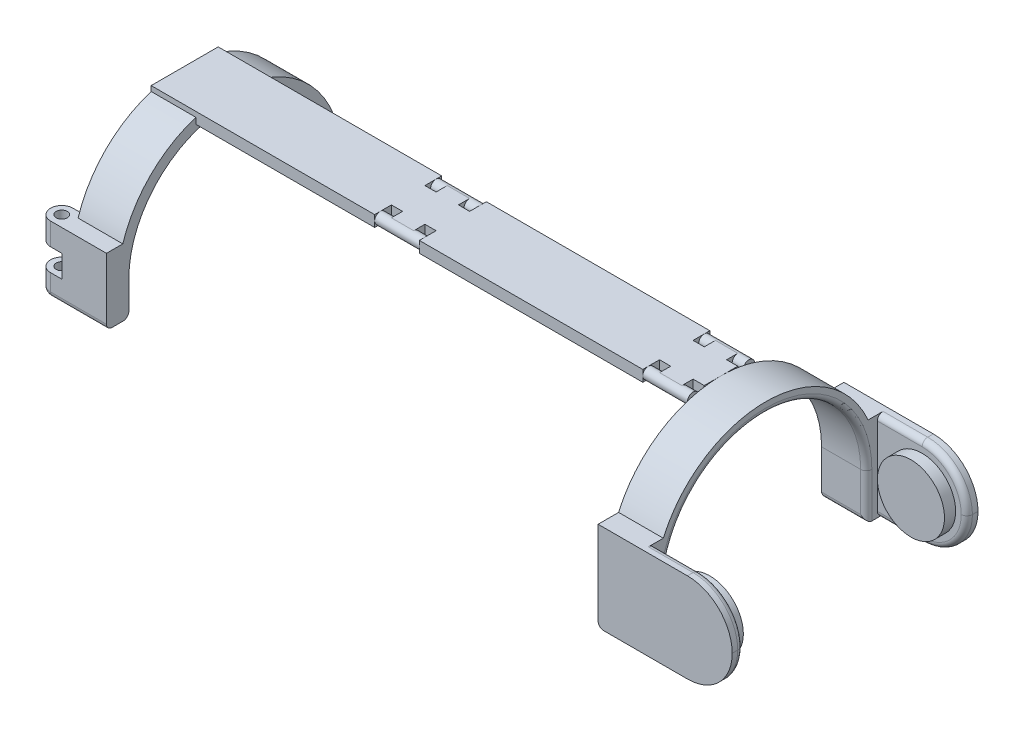
SolidWorks part; units mm, degrees
ref_plane "Front Plane" through (0, 0, 0) normal (0, 0, 1) x (1, 0, 0)
ref_plane "Top Plane" through (0, 0, 0) normal (0, 1, 0) x (1, 0, 0)
ref_plane "Right Plane" through (0, 0, 0) normal (1, 0, 0) x (0, 0, -1)
sketch "Sketch1" plane through (0, 0, 0) normal (1, 0, 0) x (0, 0, -1)
  line L0 (-45, 0) -> (-50, 0)
  line L1 (45, 0) -> (50, 0)
  arc A0 (-50, 0) -> (50, 0) centre (0, 0) cw
  arc A1 (-45, 0) -> (45, 0) centre (0, 0) cw
  dimension "D1" = 50
  dimension "D2" = 45
extrude "Boss-Extrude1" add sketch "Sketch1" along normal blind 20
sketch "Sketch3" plane through (0, 0, 0) normal (1, 0, 0) x (0, 0, -1)
  line L0 (45, 0) -> (50, 0) construction
  line L1 (45, -20) -> (55, -20)
  line L2 (45, -20) -> (45, 20)
  line L3 (45, 20) -> (55, 20)
  line L4 (55, -20) -> (55, 20)
  dimension "D1" = 40
  dimension "D2" = 10
  dimension "D3" = 20
extrude "Boss-Extrude2" add sketch "Sketch3" along normal blind 60
sketch "Sketch4" plane through (0, 0, -45) normal (0, 0, 1) x (1, 0, 0)
  line L0 (60, -20) -> (0, -20) construction
  line L1 (60, 20) -> (20, 20)
  line L2 (60, 20) -> (60, -20)
  line L3 (60, -20) -> (20, -20)
  line L4 (20, 20) -> (20, -20)
extrude "Cut-Extrude1" cut sketch "Sketch4" against normal blind 5
sketch "Sketch5" plane through (0, 0, -50) normal (0, 0, 1) x (1, 0, 0)
  line L0 (60, -20) -> (60, 20) construction
  line L1 (60, 20) -> (20, 20) construction
  circle A0 centre (40, 0) radius 15
  dimension "D1" = 30
  dimension "D2" = 20
  dimension "D3" = 20
extrude "Boss-Extrude3" add sketch "Sketch5" along normal blind 5
sketch "Sketch6" plane through (0, 0, 0) normal (-1, 0, 0) x (0, 0, 1)
  line L1 (0, 45) -> (-7.5, 45)
  line L2 (0, 45) -> (0, 50)
  line L3 (0, 50) -> (-7.5, 50)
  line L4 (-7.5, 45) -> (-7.5, 50)
  arc A0 (45, 0) -> (-45, 0) centre (0, 0) ccw construction
  dimension "D1" = 7.5
extrude "Boss-Extrude4" add sketch "Sketch6" along normal blind 20
sketch "Sketch7" plane through (0, 0, -7.5) normal (0, 0, -1) x (-1, 0, 0)
  line L0 (20, 50) -> (0, 50) construction
  line L1 (5, 50) -> (15, 50)
  line L2 (5, 50) -> (5, 45)
  line L3 (5, 45) -> (15, 45)
  line L4 (15, 50) -> (15, 45)
  line L5 (20, 45) -> (0, 45) construction
  line L6 (0, 49.4343) -> (0, 45) construction
  dimension "D1" = 10
  dimension "D2" = 5
extrude "Boss-Extrude5" add sketch "Sketch7" along normal blind 5
sketch "Sketch9" plane through (0, 0, 0) normal (1, 0, 0) x (0, 0, -1)
  line L0 (12.5, 45) -> (12.5, 50) construction
  circle A0 centre (12.5, 47.5) radius 2.5
  dimension "D1" = 5
extrude "Boss-Extrude6" add sketch "Sketch9" against normal blind 20
mirror "Mirror1" about plane through (0, 0, 0) normal (0, 0, 1) of "Boss-Extrude6", "Boss-Extrude5", "Boss-Extrude4", "Boss-Extrude3", "Cut-Extrude1", "Boss-Extrude2"
fillet "Fillet2" radius 2.5 7 edges at (20, 45, 0) (10, -20, 45) (20, -10, 45) (0, -20, -50) (10, -20, -45) (20, -10, -45) (0, -20, 50)
fillet "Fillet3" radius 20 4 edges at (60, -20, -52.5) (60, 20, -52.5) (60, -20, 52.5) (60, 20, 52.5)
fillet "Fillet4" radius 2.5 8 edges at (30, -20, -50) (54.1421, -14.1421, -50) (54.1421, 14.1421, -50) (30, -20, 50) (54.1421, -14.1421, 50) (54.1421, 14.1421, 50) (30, 20, -50) (30, 20, 50)
sketch "Sketch10" plane through (-20, 0, 0) normal (-1, 0, 0) x (0, 0, 1)
  line L0 (7.5, 50) -> (7.5, 45) construction
  line L1 (15, 45) -> (-15, 45)
  line L2 (15, 45) -> (15, 50)
  line L3 (15, 50) -> (-15, 50)
  line L4 (-15, 45) -> (-15, 50)
  line L6 (-7.5, 50) -> (-7.5, 45) construction
  point P6 (-7.5, 47.5)
  dimension "D1" = 30
  dimension "D2" = 7.5
  dimension "D3" = 5
  dimension "D4" = 2.5
extrude "Boss-Extrude9" add sketch "Sketch10" along normal blind 100
sketch "Sketch12" plane through (-120, 0, 0) normal (-1, 0, 0) x (0, 0, 1)
  line L0 (15, 50) -> (-15, 50) construction
  line L1 (-7.5, 50) -> (0, 50)
  line L2 (-7.5, 50) -> (-7.5, 45)
  line L3 (-7.5, 45) -> (0, 45)
  line L4 (0, 50) -> (0, 45)
  line L5 (-15, 45) -> (15, 45) construction
  line L6 (-15, 50) -> (-15, 45) construction
  dimension "D1" = 7.5
  dimension "D2" = 7.5
extrude "Boss-Extrude10" add sketch "Sketch12" along normal blind 20
sketch "Sketch13" plane through (0, 0, -7.5) normal (0, 0, -1) x (-1, 0, 0)
  line L0 (140, 50) -> (120, 50) construction
  line L1 (125, 50) -> (135, 50)
  line L2 (125, 50) -> (125, 45)
  line L3 (125, 45) -> (135, 45)
  line L4 (135, 50) -> (135, 45)
  line L5 (140, 45) -> (120, 45) construction
  line L6 (120, 50) -> (120, 45) construction
  dimension "D1" = 10
  dimension "D2" = 5
extrude "Boss-Extrude11" add sketch "Sketch13" along normal blind 5
sketch "Sketch14" plane through (-135, 0, 0) normal (-1, 0, 0) x (0, 0, 1)
  line L0 (-12.5, 45) -> (-12.5, 50) construction
  circle A0 centre (-12.5, 47.5) radius 2.5
  dimension "D1" = 5
extrude "Boss-Extrude12" add sketch "Sketch14" along normal blind 5 and the other way blind 15
mirror "Mirror2" about plane through (-140, 50, 0) normal (0, 0, -1) of "Boss-Extrude12", "Boss-Extrude11", "Boss-Extrude10"
sketch "Sketch15" plane through (-140, 0, 0) normal (-1, 0, 0) x (0, 0, 1)
  line L1 (15, 45) -> (-15, 45)
  line L2 (15, 45) -> (15, 50)
  line L3 (15, 50) -> (-15, 50)
  line L4 (-15, 45) -> (-15, 50)
extrude "Boss-Extrude13" add sketch "Sketch15" along normal blind 100
sketch "Sketch16" plane through (-240, 0, 0) normal (-1, 0, 0) x (0, 0, 1)
  line L0 (50, 0) -> (45, 0)
  line L1 (-45, 0) -> (-50, 0)
  arc A0 (45, 0) -> (-45, 0) centre (0, 0) ccw
  arc A1 (0, 45) -> (-45, 0) centre (0, 0) ccw construction
  arc A2 (50, 0) -> (-50, 0) centre (0, 0) ccw
  dimension "D1" = 50
extrude "Boss-Extrude14" add sketch "Sketch16" against normal blind 20
sketch "Sketch17" plane through (-240, 0, 0) normal (-1, 0, 0) x (0, 0, 1)
  line L1 (45, 0) -> (55, 0)
  line L2 (45, 0) -> (45, 15)
  line L3 (45, 15) -> (55, 15)
  line L4 (55, 0) -> (55, 15)
  dimension "D1" = 15
  dimension "D2" = 10
extrude "Boss-Extrude15" add sketch "Sketch17" against normal blind 20 and the other way blind 10
sketch "Sketch18" plane through (0, 0, 55) normal (0, 0, 1) x (1, 0, 0)
  line L1 (-250, 0) -> (-240, 0)
  line L2 (-250, 0) -> (-250, 5)
  line L3 (-250, 5) -> (-240, 5)
  line L4 (-240, 0) -> (-240, 5)
  dimension "D1" = 10
  dimension "D2" = 5
extrude "Cut-Extrude2" cut sketch "Sketch18" against normal up to next
sketch "Sketch19" plane through (0, 5, 0) normal (0, -1, 0) x (1, 0, 0)
  circle A0 centre (-245, 50) radius 2.5
  dimension "D1" = 5
extrude "Cut-Extrude3" cut sketch "Sketch19" against normal blind 10
mirror "Mirror3" of "Cut-Extrude3", "Cut-Extrude2", "Boss-Extrude15"
fillet "Fillet5" radius 5 4 edges at (-250, -10, 45) (-250, -10, 55) (-250, 10, 55) (-250, 10, 45)
fillet "Fillet6" radius 2.5 8 edges at (-240, 0, -47.5) (-230, 0, -50) (-220, 0, -47.5) (-230, 0, -45) (-232.5, -15, 45) (-232.5, -15, 55) (-248.5355, -15, 53.5355) (-248.5355, -15, 46.4645)
